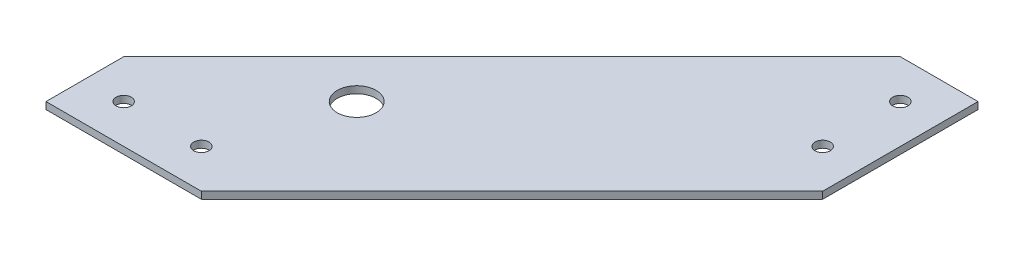
SolidWorks part; units mm, degrees
ref_plane "Front Plane" through (0, 0, 0) normal (0, 0, 1) x (1, 0, 0)
ref_plane "Top Plane" through (0, 0, 0) normal (0, 1, 0) x (1, 0, 0)
ref_plane "Right Plane" through (0, 0, 0) normal (1, 0, 0) x (0, 0, -1)
sketch "Sketch1" plane through (0, 0, 0) normal (0, 1, 0) x (1, 0, 0)
  line L0 (0, 0) -> (0, 152.4)
  line L1 (0, 152.4) -> (-25.4, 152.4)
  line L2 (-25.4, 152.4) -> (-152.4, 25.4)
  line L3 (-152.4, 25.4) -> (-152.4, 0)
  line L4 (-152.4, 0) -> (0, 0)
  circle A0 centre (-12.7, 12.7) radius 2.4892
  circle A1 centre (-38.1, 12.7) radius 2.4892
  circle A2 centre (-63.5, 12.7) radius 2.4892
  circle A3 centre (-88.9, 12.7) radius 2.4892
  circle A4 centre (-114.3, 12.7) radius 2.4892
  circle A5 centre (-12.7, 38.1) radius 2.4892
  circle A6 centre (-12.7, 63.5) radius 2.4892
  circle A7 centre (-12.7, 88.9) radius 2.4892
  circle A8 centre (-12.7, 114.3) radius 2.4892
  circle A9 centre (-139.7, 12.7) radius 2.4892
  circle A13 centre (-12.7, 139.7) radius 2.4892
  circle A17 centre (-101.6, 50.8) radius 6.35
  dimension "D4" = 12.7
  dimension "D5" = 12.7
  dimension "D8" = 12.7
  dimension "D1" = 152.4
  dimension "D2" = 25.4
  dimension "D3" = 152.4
  dimension "D9" = 101.6
  dimension "D10" = 50.8
  dimension "D11" = 25.4
  dimension "D6" = 6
  dimension "D7" = 6
extrude "Boss-Extrude2" add sketch "Sketch1" along normal mid plane 2.286
sketch "Sketch2" plane through (0, 1.143, 0) normal (0, 1, 0) x (1, 0, 0)
  line L0 (0, 0) -> (0, 101.6)
  line L1 (0, 0) -> (0, 152.4) construction
  line L2 (0, 101.6) -> (-101.6, 0)
  line L3 (-152.4, 0) -> (0, 0) construction
  line L4 (-101.6, 0) -> (0, 0)
  dimension "D1" = 45
  dimension "D2" = 101.6
  dimension "D3" = 101.6
extrude "Cut-Extrude1" cut sketch "Sketch2" against normal through all
sketch "Sketch3" plane through (0, 1.143, 0) normal (0, 1, 0) x (1, 0, 0)
  line L0 (-101.6, 0) -> (-101.6, 15.1204)
  line L1 (-101.6, 15.1204) -> (-15.6123, 101.1081)
  line L2 (-15.6123, 101.1081) -> (0, 101.6)
  line L3 (0, 101.6) -> (-101.6, 0)
extrude "Boss-Extrude3" add sketch "Sketch3" against normal blind 2.286
equation "\"0.09inin\"=0.1"
